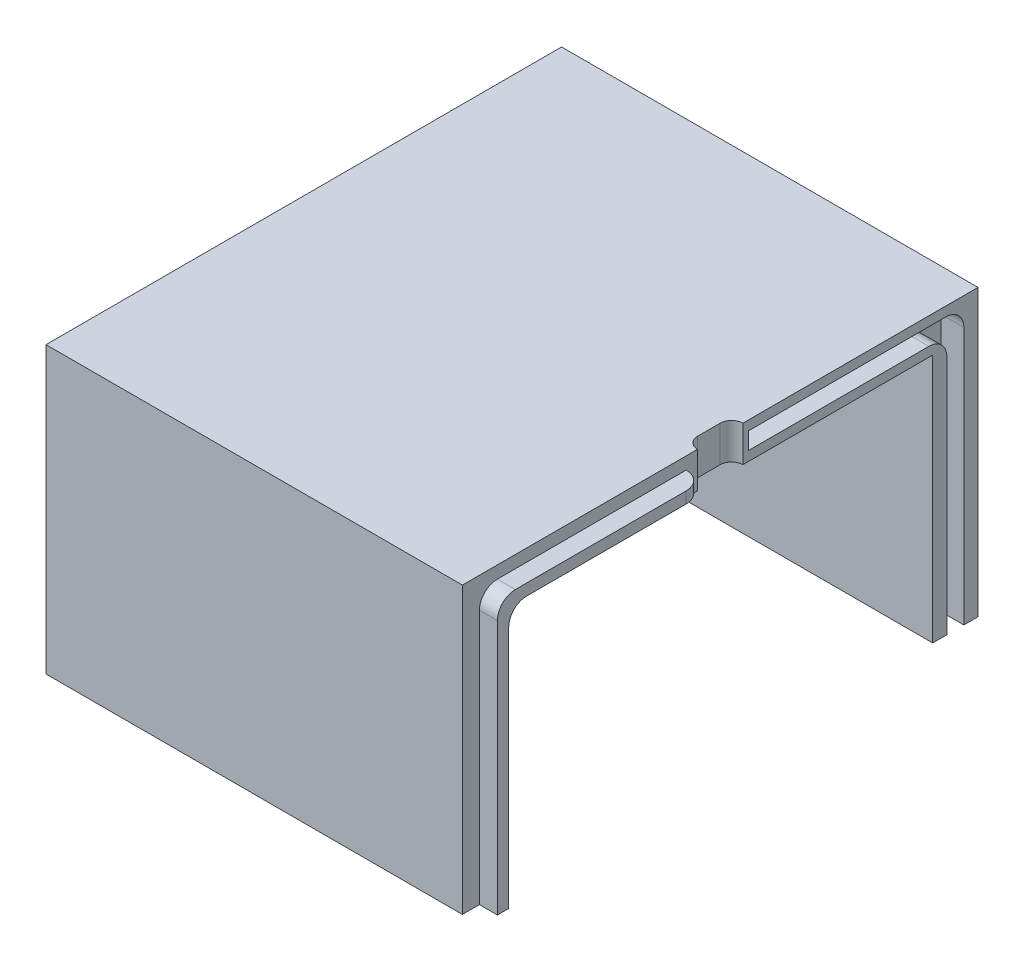
SolidWorks part; units mm, degrees
material "6061 Alloy"
ref_plane "Front Plane" through (0, 0, 0) normal (0, 0, 1) x (1, 0, 0)
ref_plane "Top Plane" through (0, 0, 0) normal (0, 1, 0) x (1, 0, 0)
ref_plane "Right Plane" through (0, 0, 0) normal (1, 0, 0) x (0, 0, -1)
sketch "MainSketch" plane through (0, 0, 0) normal (0, 1, 0) x (1, 0, 0)
  line L0 (0, -4) -> (-32.75, -4)
  line L1 (0, 0) -> (-36.75, 0)
  line L2 (0, 0) -> (0, -45.5)
  line L3 (0, -45.5) -> (-36.75, -45.5)
  line L4 (-36.75, 0) -> (-36.75, -45.5)
  line L5 (-32.75, -4) -> (-32.75, -41.5)
  line L6 (-32.75, -41.5) -> (0, -41.5)
  line L7 (31.75, -5) -> (-31.75, -5) construction
  line L8 (-31.75, -5) -> (-31.75, -40.5) construction
  line L9 (-31.75, -40.5) -> (31.75, -40.5) construction
  line L10 (0, -21.75) -> (0, -23.75) construction
  line L11 (1, -21.75) -> (1, -23.75)
  line L12 (-1, -21.75) -> (-1, -23.75)
  arc A0 (1, -21.75) -> (-1, -21.75) centre (0, -21.75) ccw
  arc A1 (-1, -23.75) -> (1, -23.75) centre (0, -23.75) ccw
  point P7 (-10, -2.5)
  point P10 (-34.25, -2.5)
  point P11 (-34.25, -43)
  point P12 (-10, -43)
  point P17 (0, -22.75)
  point P24 (-18.375, -2.5)
  point P26 (-18.375, -43)
  dimension "D14" = 1
  dimension "D1" = 4
  dimension "D2" = 4
  dimension "D3" = 4
  dimension "D4" = 36.75
  dimension "D6" = 5
  dimension "D7" = 5
  dimension "D8" = 5
  dimension "D9" = 2.5
  dimension "D10" = 2.5
  dimension "D11" = 10
  dimension "D12" = 10
  dimension "D13" = 2.5
  dimension "D15" = 2
  dimension "D5" = 35.5
  dimension "D16" = 63.5
  dimension "D17" = 18.375
extrude "Wall" add sketch "MainSketch" along normal blind 22 contours L6 L5 L0 L2 L1 L4 L3 region at (-16.375, 0, 3.4151)
extrude "Roof" add sketch "MainSketch<3>" along normal blind 3.175 from surface contours L5 L6 L2 L0 | L6 L5 L0 L2 L1 L4 L3 region at (-16.4214, 0, 22.75) region at (-16.375, 0, 3.4151) starting at face at (-17.375, 22, 22.75)
sketch "MainSketch<3>" plane through (0, 0, 0) normal (0, 1, 0) x (1, 0, 0) same geometry as "MainSketch"
hole_wizard "#2-56 Tapped Hole1" positions "3DSketch1" profile "Sketch2" tap size "#2-56" standard "ANSI Inch"
sketch3d "3DSketch1"
  point P19 (-18.375, 0, 43)
  point P22 (-18.375, 0, 2.5)
sketch "Sketch2" plane through (-18.375, 0, 43) normal (1, 0, 0) x (0, 0, -1)
  line L0 (0, 0) -> (0, 6.2642)
  line L1 (0, 6.2642) -> (0.889, 5.73)
  line L2 (0.889, 5.73) -> (0.889, 0)
  line L5 (0.889, 0) -> (0, 0)
  line L10 (0, 6.2642) -> (-0.889, 5.73) construction
  line L11 (0, -6.35) -> (0, 107.95) construction
  dimension "Tap Drill Dia." = 1.778
  dimension "Tap Drill Depth" = 5.73
  dimension "Drill Angle" = 118
cosmetic thread "Hole Thread1" parameters "D1"=4.37, "D2"=2.1844
cosmetic thread "Hole Thread2" parameters "D1"=4.37, "D2"=2.1844
sketch "Sketch3" plane through (0, 0, 0) normal (1, 0, 0) x (0, 0, -1)
  line L0 (-44, 0) -> (-44, 24.0875)
  line L1 (-41.5, 0) -> (-45.5, 0) construction
  line L2 (-44, 24.0875) -> (-25.75, 24.0875)
  line L3 (-1.25, 24.3375) -> (-1.25, 0)
  line L4 (0, 0) -> (-4, 0) construction
  line L5 (-43, 0) -> (-43, 23.0875)
  line L6 (-43, 23.0875) -> (-25.75, 23.0875)
  line L7 (-2.75, 22.8375) -> (-2.75, 0)
  line L8 (-44, 0) -> (-43, 0) construction
  line L9 (-45.5, 25.175) -> (-45.5, 0) construction
  line L10 (-2.75, 0) -> (-1.25, 0)
  line L11 (-20.25, 24.3375) -> (-1.25, 24.3375)
  line L12 (-20.25, 22.8375) -> (-20.25, 24.3375)
  line L13 (-45.5, 25.175) -> (-24.75, 25.175) construction
  line L14 (-24.75, 25.175) -> (-24.75, 22) construction
  line L15 (-44, 0) -> (-43, 0)
  line L16 (-25.75, 24.0875) -> (-25.75, 23.0875)
  line L18 (-20.25, 22.8375) -> (-2.75, 22.8375)
  line L19 (0, 25.175) -> (0, 0) construction
  line L20 (-20.75, 25.175) -> (-20.75, 22) construction
  line L21 (-20.75, 25.175) -> (0, 25.175) construction
  point P10 (-43.5, 0)
  point P17 (-2, 0)
  point P18 (-25.75, 23.5875)
  point P30 (-20.25, 23.5875)
  dimension "D2" = 1
  dimension "D4" = 2
  dimension "D7" = 1
  dimension "D1" = 1.5875
  dimension "D3" = 1
  dimension "D5" = 2
  dimension "D6" = 1.5
  dimension "D8" = 1.5
  dimension "D9" = 0.5
  dimension "D10" = 1.5875
extrude "Boss-Extrude1" add sketch "Sketch3" along normal blind 1.5875 contours L16 L2 L0 L15 L5 L6 region at (0, 12.0437, 43.6978)
extrude "Cut-Extrude3" cut sketch "Sketch3<3>" against normal blind 2 contours L12 L18 L7 L10 L3 L11 region at (0, 12.1688, 1.5588)
sketch "Sketch3<3>" plane through (0, 0, 0) normal (1, 0, 0) x (0, 0, -1) same geometry as "Sketch3"
fillet "Fillet1" radius 1.5875 6 edges at (0.7937, 23.0875, 43) (0.7937, 24.0875, 44) (1.5875, 23.5875, 25.75) (-1, 24.3375, 1.25) (-1, 22.8375, 2.75) (-2, 23.5875, 20.25)
equation "\"D2@MainSketch\" = \"D1@MainSketch\""
equation "\"D3@MainSketch\" = \"D2@MainSketch\""
equation "\"D7@MainSketch\" = \"D6@MainSketch\""
equation "\"D8@MainSketch\" = \"D6@MainSketch\""
equation "\"D9@MainSketch\" = \"D7@MainSketch\" / 2"
equation "\"D10@MainSketch\" = \"D9@MainSketch\""
equation "\"D12@MainSketch\" = \"D11@MainSketch\""
equation "\"D13@MainSketch\" = \"D10@MainSketch\""
equation "\"D4@MainSketch\"=(\"D16@MainSketch\"+\"D6@MainSketch\"*2)/2"
equation "\"side_thick\"= 4"
equation "\"D1@MainSketch\"=\"side_thick\""
equation "\"top_thick\"=3.175"
equation "\"D1@Roof\"=\"top_thick\""
equation "\"D4@Sketch3\"=\"side_thick\"/2"
equation "\"D17@MainSketch\"=\"D4@MainSketch\"/2"
equation "\"D3@Sketch3\"=\"D2@Sketch3\""
equation "\"D8@Sketch3\"=\"D6@Sketch3\""
equation "\"D9@Sketch3\"=\"D6@Sketch3\"-\"D7@Sketch3\""
equation "\"D10@Sketch3\"=\"D1@Sketch3\""
